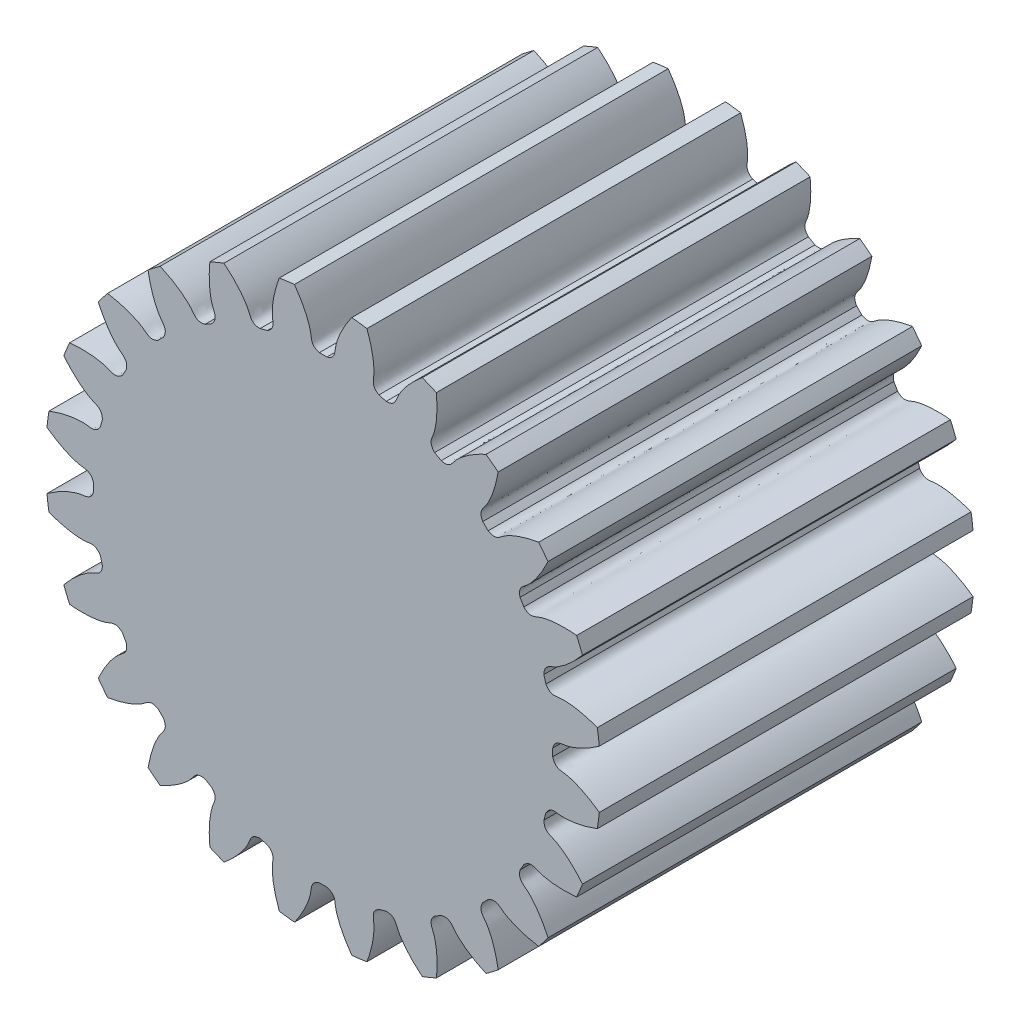
SolidWorks part; units mm, degrees
ref_plane "前视基准面" through (0, 0, 0) normal (0, 0, 1) x (1, 0, 0)
ref_plane "上视基准面" through (0, 0, 0) normal (0, 1, 0) x (1, 0, 0)
ref_plane "右视基准面" through (0, 0, 0) normal (1, 0, 0) x (0, 0, -1)
sketch "草图1" plane through (0, 0, 0) normal (0, 0, 1) x (1, 0, 0)
  circle A0 centre (0, 0) radius 13
extrude "凸台-拉伸1" add sketch "草图1" along normal blind 30
ref_axis "基准轴1" through (0, 0, -1.5) along (0, 0, 1)
sketch "草图2" plane through (0, 0, 0) normal (0, 0, 1) x (1, 0, 0)
  line L0 (0, 0) -> (0, 13) construction
  circle A0 centre (0, 0) radius 13 construction
  arc A1 (0.1768, 10.7485) -> (-0.1768, 10.7485) centre (0, 0) ccw
  arc A2 (3.1156, 14.6941) -> (-3.1156, 14.6941) centre (0, 0) ccw
  spline S0 degree 3 poles (0.1768, 10.7485) (0.5679, 10.8569) (0.539, 11.1157) (0.5863, 11.3727) (0.593, 11.4058) (0.6014, 11.4432) (0.6117, 11.4849) (0.6239, 11.5306) (0.6383, 11.5804) (0.655, 11.6343) (0.6742, 11.6921) (0.6961, 11.7537) (0.7208, 11.8191) (0.7484, 11.8882) (0.7793, 11.9609) (0.8133, 12.0371) (0.8509, 12.1166) (0.892, 12.1995) (0.9369, 12.2854) (0.9856, 12.3745) (1.0383, 12.4664) (1.0952, 12.5612) (1.1564, 12.6586) (1.222, 12.7585) (1.2921, 12.8608) (1.3669, 12.9654) (1.4464, 13.0721) (1.5309, 13.1807) (1.6203, 13.2911) (1.7148, 13.4032) (1.8145, 13.5167) (1.9196, 13.6315) (2.03, 13.7475) (2.1458, 13.8645) (2.2673, 13.9822) (2.3943, 14.1006) (2.5271, 14.2195) (2.6656, 14.3386) (2.8604, 14.4994) (3.0119, 14.6169) (3.1156, 14.6941) knots 0 0 0 0 0.143961 0.149818 0.156577 0.164236 0.172796 0.182258 0.19262 0.203884 0.216049 0.229115 0.243082 0.25795 0.273719 0.290389 0.30796 0.326433 0.345806 0.366081 0.387257 0.409333 0.432311 0.45619 0.48097 0.506651 0.533234 0.560717 0.589101 0.618387 0.648574 0.679661 0.71165 0.74454 0.778331 0.813023 0.848616 0.885111 0.922506 1 1 1 1
  spline S1 degree 3 poles (-0.1768, 10.7485) (-0.5679, 10.8569) (-0.539, 11.1157) (-0.5863, 11.3727) (-0.593, 11.4058) (-0.6014, 11.4432) (-0.6117, 11.4849) (-0.6239, 11.5306) (-0.6383, 11.5804) (-0.655, 11.6343) (-0.6742, 11.6921) (-0.6961, 11.7537) (-0.7208, 11.8191) (-0.7484, 11.8882) (-0.7793, 11.9609) (-0.8133, 12.0371) (-0.8509, 12.1166) (-0.892, 12.1995) (-0.9369, 12.2854) (-0.9856, 12.3745) (-1.0383, 12.4664) (-1.0952, 12.5612) (-1.1564, 12.6586) (-1.222, 12.7585) (-1.2921, 12.8608) (-1.3669, 12.9654) (-1.4464, 13.0721) (-1.5309, 13.1807) (-1.6203, 13.2911) (-1.7148, 13.4032) (-1.8145, 13.5167) (-1.9196, 13.6315) (-2.03, 13.7475) (-2.1458, 13.8645) (-2.2673, 13.9822) (-2.3943, 14.1006) (-2.5271, 14.2195) (-2.6656, 14.3386) (-2.8604, 14.4994) (-3.0119, 14.6169) (-3.1156, 14.6941) knots 0 0 0 0 0.143961 0.149818 0.156577 0.164236 0.172796 0.182258 0.19262 0.203884 0.216049 0.229115 0.243082 0.25795 0.273719 0.290389 0.30796 0.326433 0.345806 0.366081 0.387257 0.409333 0.432311 0.45619 0.48097 0.506651 0.533234 0.560717 0.589101 0.618387 0.648574 0.679661 0.71165 0.74454 0.778331 0.813023 0.848616 0.885111 0.922506 1 1 1 1
extrude "切除-拉伸1" cut sketch "草图2" along normal through all
pattern_circular "阵列(圆周)1" count 24 every 15 about axis through (0, 0, -1.5) along (0, 0, 1) of "切除-拉伸1"
sketch "草图3" plane through (0, 0, 0) normal (0, 0, 1) x (1, 0, 0)
  circle A0 centre (0, 0) radius 12 construction
  dimension "Dn" = 24
sketch "草图4" plane through (0, 0, 30) normal (0, 0, 1) x (1, 0, 0)
  circle A0 centre (0, 0) radius 18.0986
extrude "切除-拉伸2" cut sketch "草图4" against normal offset from surface (12.5 mm away) 17.5 up to face at (0, 0, 0)
